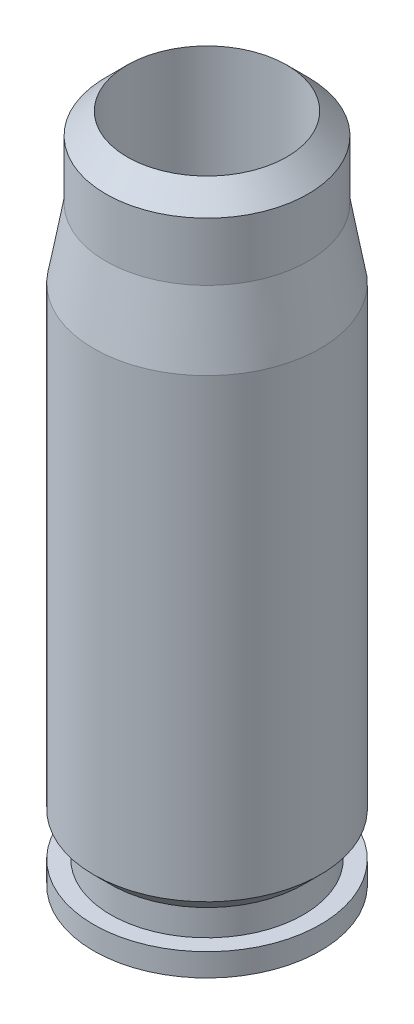
SolidWorks part; units mm, degrees
ref_plane "정면" through (0, 0, 0) normal (0, 0, 1) x (1, 0, 0)
ref_plane "윗면" through (0, 0, 0) normal (0, 1, 0) x (1, 0, 0)
ref_plane "우측면" through (0, 0, 0) normal (1, 0, 0) x (0, 0, -1)
sketch "스케치3" plane through (0, 0, 0) normal (1, 0, 0) x (0, 0, -1)
  line L0 (0, 0) -> (0, 33.9005) construction
  line L1 (4.5, 0) -> (9.95, 0)
  line L2 (9.95, 0) -> (9.95, 2)
  line L3 (9.95, 2) -> (8.4586, 2)
  line L4 (8.4586, 2) -> (8.4586, 4.3)
  line L5 (4.5, 0) -> (4.5, 12)
  line L6 (9.95, 5.7914) -> (9.95, 45.7914)
  line L7 (9.95, 45.7914) -> (8.875, 51.888)
  line L8 (8.875, 51.888) -> (8.875, 60)
  line L9 (8.875, 60) -> (7, 60)
  line L10 (7, 60) -> (7, 12)
  line L11 (8.4586, 4.3) -> (9.95, 5.7914)
  line L12 (4.5, 12) -> (7, 12)
  dimension "D1" = 9.95
  dimension "D2" = 2
  dimension "D3" = 2.3
  dimension "D4" = 135
  dimension "D5" = 40
  dimension "D6" = 170
  dimension "D7" = 14
  dimension "D8" = 4.5
  dimension "D9" = 12
  dimension "D10" = 60
  dimension "D11" = 17.75
revolve "회전1" add sketch "스케치3" angle 360 about L0
chamfer "모따기1" distance 3 angle 45 1 edges at (0, 60, -8.875)
